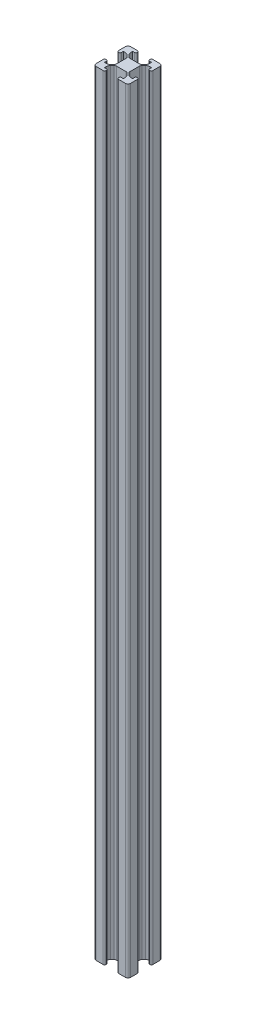
SolidWorks part; units mm, degrees
ref_plane "Front" through (0, 0, 0) normal (0, 0, 1) x (1, 0, 0)
ref_plane "Top" through (0, 0, 0) normal (0, 1, 0) x (1, 0, 0)
ref_plane "Right" through (0, 0, 0) normal (1, 0, 0) x (0, 0, -1)
sketch "Sketch2" plane through (0, 0, 0) normal (0, 1, 0) x (1, 0, 0)
  line L0 (-5.4, 4.8697) -> (-4.3393, 3.809)
  line L1 (-8.5, 10) -> (-4.4, 10)
  line L3 (-8.5, -10) -> (-4.4, -10)
  line L4 (10, 8.5) -> (10, 4.4)
  line L5 (-10, 10) -> (-9.5607, 9.5607) construction
  line L6 (-10, -10) -> (-9.5607, -9.5607) construction
  line L7 (-2.7483, 3.9) -> (2.7483, 3.9)
  line L8 (-3.9, 2.7483) -> (-3.9, -2.7483)
  line L9 (-2.7483, -3.9) -> (2.7483, -3.9)
  line L10 (3.9, 2.7483) -> (3.9, -2.7483)
  line L11 (-5.5, -8.2) -> (-4.4, -8.2)
  line L12 (-3.6, -9.2) -> (-3.6, -9)
  line L13 (-4.8697, 5.4) -> (-3.809, 4.3393)
  line L14 (4.8697, 5.4) -> (3.809, 4.3393)
  line L15 (5.4, 4.8697) -> (4.3393, 3.809)
  line L16 (-5.5, -8.2) -> (-5.5, -7.2)
  line L17 (9.5607, -9.5607) -> (10, -10) construction
  line L18 (-3.809, -4.3393) -> (-4.8697, -5.4)
  line L19 (-4.3393, -3.809) -> (-5.4, -4.8697)
  line L20 (3.809, -4.3393) -> (4.8697, -5.4)
  line L21 (4.3393, -3.809) -> (5.4, -4.8697)
  line L22 (9.5607, 9.5607) -> (10, 10) construction
  line L23 (8.5, -10) -> (4.4, -10)
  line L24 (3.6, -9.2) -> (3.6, -9)
  line L25 (5.5, -8.2) -> (4.4, -8.2)
  line L26 (0, 7.192) -> (0, -12.1556) construction
  line L27 (5.5, -8.2) -> (5.5, -7.2)
  line L28 (-8.2, 5.5) -> (-7.2, 5.5)
  line L29 (-8.2, 5.5) -> (-8.2, 4.4)
  line L30 (-10, 8.5) -> (-10, 4.4)
  line L31 (-8.2, -5.5) -> (-7.2, -5.5)
  line L32 (-10, -8.5) -> (-10, -4.4)
  line L33 (-8.2, -5.5) -> (-8.2, -4.4)
  line L34 (5.5, 8.2) -> (5.5, 7.2)
  line L35 (5.5, 8.2) -> (4.4, 8.2)
  line L36 (8.5, 10) -> (4.4, 10)
  line L37 (-5.5, 8.2) -> (-5.5, 7.2)
  line L38 (3.6, 9.2) -> (3.6, 9)
  line L39 (-5.5, 8.2) -> (-4.4, 8.2)
  line L40 (8.2, -5.5) -> (7.2, -5.5)
  line L41 (8.2, -5.5) -> (8.2, -4.4)
  line L42 (-3.6, 9.2) -> (-3.6, 9)
  line L43 (8.2, 5.5) -> (7.2, 5.5)
  line L44 (10, -4.4) -> (10, -8.5)
  line L45 (8.2, 5.5) -> (8.2, 4.4)
  line L46 (9, -3.6) -> (9.2, -3.6)
  line L47 (9, 3.6) -> (9.2, 3.6)
  line L48 (-9.2, 3.6) -> (-9, 3.6)
  line L49 (-9.2, -3.6) -> (-9, -3.6)
  line L52 (-8.5, 10) -> (-4.4, 10) [skipped]
  line L53 (10, -8.5) -> (10, -4.4) [skipped]
  line L54 (10, 8.5) -> (10, 4.4) [skipped]
  arc A0 (-10, -8.5) -> (-8.5, -10) centre (-8.5, -8.5) ccw
  arc A1 (8.5, -10) -> (10, -8.5) centre (8.5, -8.5) ccw
  arc A2 (8.5, 10) -> (10, 8.5) centre (8.5, 8.5) cw
  arc A3 (-8.5, 10) -> (-10, 8.5) centre (-8.5, 8.5) ccw
  arc A4 (-3.9, -2.7483) -> (-4.3393, -3.809) centre (-5.4, -2.7483) cw
  arc A5 (-2.7483, -3.9) -> (-3.809, -4.3393) centre (-2.7483, -5.4) ccw
  arc A6 (2.7483, -3.9) -> (3.809, -4.3393) centre (2.7483, -5.4) cw
  arc A7 (3.9, -2.7483) -> (4.3393, -3.809) centre (5.4, -2.7483) ccw
  arc A8 (3.9, 2.7483) -> (4.3393, 3.809) centre (5.4, 2.7483) cw
  arc A9 (2.7483, 3.9) -> (3.809, 4.3393) centre (2.7483, 5.4) ccw
  arc A10 (-2.7483, 3.9) -> (-3.809, 4.3393) centre (-2.7483, 5.4) cw
  arc A11 (-3.9, 2.7483) -> (-4.3393, 3.809) centre (-5.4, 2.7483) ccw
  arc A12 (-5.5, -7.2) -> (-4.8697, -5.4) centre (-2.6148, -7.2) cw
  arc A13 (-3.6, -9.2) -> (-4.4, -10) centre (-4.4, -9.2) cw
  arc A14 (-3.6, -9) -> (-4.4, -8.2) centre (-4.4, -9) ccw
  arc A15 (3.6, -9.2) -> (4.4, -10) centre (4.4, -9.2) ccw
  arc A16 (3.6, -9) -> (4.4, -8.2) centre (4.4, -9) cw
  arc A17 (5.5, -7.2) -> (4.8697, -5.4) centre (2.6148, -7.2) ccw
  arc A18 (-7.2, 5.5) -> (-5.4, 4.8697) centre (-7.2, 2.6148) cw
  arc A19 (-9, 3.6) -> (-8.2, 4.4) centre (-9, 4.4) ccw
  arc A20 (-9.2, 3.6) -> (-10, 4.4) centre (-9.2, 4.4) cw
  arc A21 (-7.2, -5.5) -> (-5.4, -4.8697) centre (-7.2, -2.6148) ccw
  arc A22 (-9, -3.6) -> (-8.2, -4.4) centre (-9, -4.4) cw
  arc A23 (-9.2, -3.6) -> (-10, -4.4) centre (-9.2, -4.4) ccw
  arc A24 (5.5, 7.2) -> (4.8697, 5.4) centre (2.6148, 7.2) cw
  arc A25 (3.6, 9) -> (4.4, 8.2) centre (4.4, 9) ccw
  arc A26 (3.6, 9.2) -> (4.4, 10) centre (4.4, 9.2) cw
  arc A27 (-5.5, 7.2) -> (-4.8697, 5.4) centre (-2.6148, 7.2) ccw
  arc A28 (-3.6, 9) -> (-4.4, 8.2) centre (-4.4, 9) cw
  arc A29 (-3.6, 9.2) -> (-4.4, 10) centre (-4.4, 9.2) ccw
  arc A30 (7.2, -5.5) -> (5.4, -4.8697) centre (7.2, -2.6148) cw
  arc A31 (9, -3.6) -> (8.2, -4.4) centre (9, -4.4) ccw
  arc A32 (9.2, -3.6) -> (10, -4.4) centre (9.2, -4.4) cw
  arc A33 (7.2, 5.5) -> (5.4, 4.8697) centre (7.2, 2.6148) ccw
  arc A34 (9, 3.6) -> (8.2, 4.4) centre (9, 4.4) cw
  arc A35 (9.2, 3.6) -> (10, 4.4) centre (9.2, 4.4) ccw
  point P0 (0, 0)
  point P6 (0, 0)
  point P41 (-3.9, -3.3697)
  point P44 (-3.3697, -3.9)
  point P47 (3.3697, -3.9)
  point P50 (3.9, -3.3697)
  dimension "D5" = 1.5
  dimension "D3" = 1.5
  dimension "D9" = 0.8
  dimension "D1" = 20
  dimension "D2" = 20
  dimension "D4" = 4
  dimension "D6" = 0.75
  dimension "D8" = 1.8
  dimension "D10" = 1
  dimension "D7" = 2
extrude "Boss-Extrude1" add sketch "Sketch2" along normal blind 450
